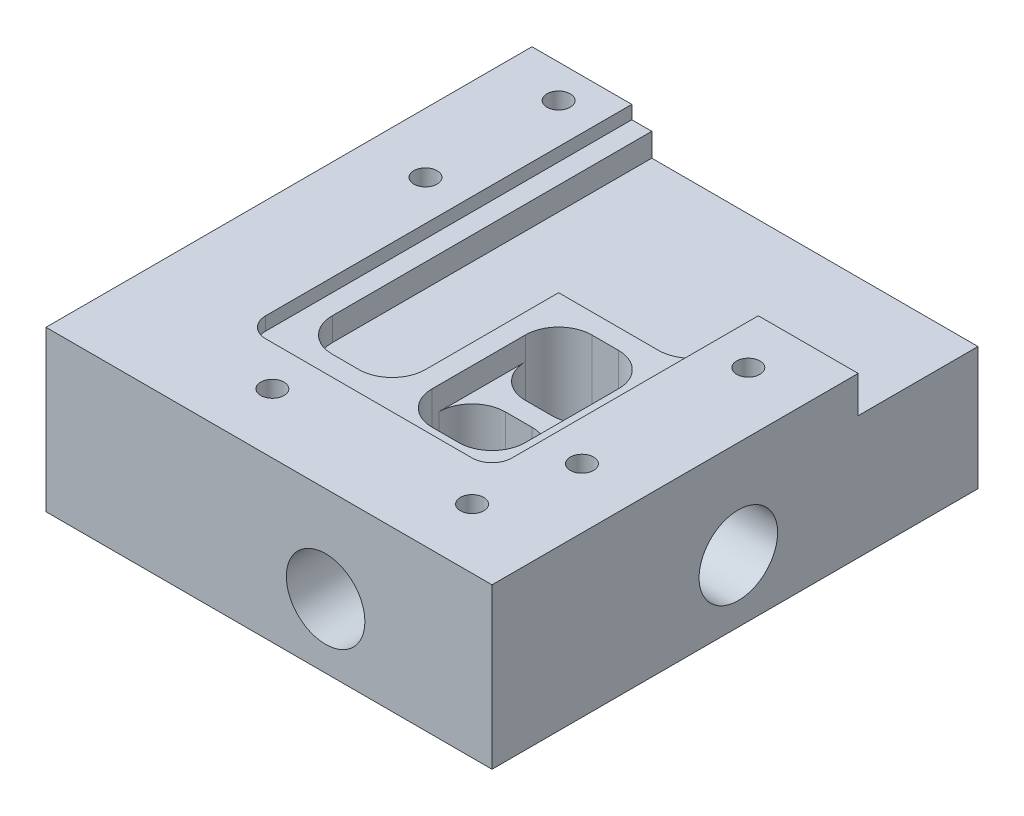
SolidWorks part; units mm, degrees
ref_plane "Front" through (0, 0, 0) normal (0, 0, 1) x (1, 0, 0)
ref_plane "Top" through (0, 0, 0) normal (0, 1, 0) x (1, 0, 0)
ref_plane "Right" through (0, 0, 0) normal (1, 0, 0) x (0, 0, -1)
sketch "Sketch1" plane through (0, 0, 0) normal (0, 1, 0) x (1, 0, 0)
  line L1 (0, 0) -> (67, 0)
  line L2 (0, 0) -> (0, 73)
  line L3 (0, 73) -> (67, 73)
  line L4 (67, 0) -> (67, 73)
  dimension "D1" = 73
  dimension "D2" = 67
extrude "Boss-Extrude1" add sketch "Sketch1" along normal blind 15
sketch "Sketch5" plane through (0, 15, 0) normal (0, 1, 0) x (1, 0, 0)
  line L0 (32, 20) -> (18, 20)
  line L1 (32, 15) -> (52, 15)
  line L2 (32, 20) -> (32, 45)
  line L3 (32, 45) -> (52, 45)
  line L4 (52, 15) -> (52, 45)
  line L5 (18, 20) -> (18, 73)
  line L6 (67, 73) -> (0, 73) construction
  line L7 (0, 0) -> (67, 0) construction
  line L8 (18, 73) -> (15, 73)
  line L9 (67, 0) -> (67, 73) construction
  line L10 (15, 73) -> (15, 15)
  line L11 (15, 15) -> (32, 15)
  dimension "D1" = 20
  dimension "D2" = 30
  dimension "D3" = 15
  dimension "D4" = 15
  dimension "D5" = 5
  dimension "D6" = 3
  dimension "D7" = 37
extrude "Boss-Extrude2" add sketch "Sketch5" along normal blind 3.5
sketch "Sketch6" plane through (0, 18.5, 0) normal (0, 1, 0) x (1, 0, 0)
  line L0 (32, 32.5) -> (21.1856, 32.5) construction
  line L1 (35, 42) -> (49, 42)
  line L2 (35, 42) -> (35, 18)
  line L3 (35, 18) -> (49, 18)
  line L4 (49, 42) -> (49, 18)
  line L5 (32, 45) -> (32, 20) construction
  line L6 (21.1856, 32.5) -> (42, 45) construction
  line L7 (52, 45) -> (32, 45) construction
  line L8 (42, 45) -> (42, -11.0626) construction
  line L9 (15, 15) -> (52, 15) construction
  line L10 (32, 45) -> (32, 20) construction
  line L11 (52, 45) -> (32, 45) construction
  dimension "D1" = 3
  dimension "D2" = 3
  dimension "D3" = 3
extrude "Cut-Extrude2" cut sketch "Sketch6" against normal blind 16
sketch "Sketch8" plane through (0, 0, -18) normal (0, 0, -1) x (-1, 0, 0)
  line L4 (-49, 2.5) -> (-35, 2.5)
  line L5 (-35, 18.5) -> (-49, 18.5)
  line L6 (-49, 18.5) -> (-49, 2.5)
  line L7 (-49, 2.5) -> (-35, 2.5)
  line L8 (-35, 2.5) -> (-35, 18.5)
  line L9 (-35, 18.5) -> (-49, 18.5) construction
  line L10 (-49, 18.5) -> (-49, 2.5) construction
  line L12 (-35, 2.5) -> (-35, 18.5) construction
  circle A0 centre (-42, 6.1554) radius 4
  dimension "D1" = 8
  dimension "D4" = 7
extrude "Cut-Extrude4" cut sketch "Sketch8" against normal through all contours A0
sketch "Sketch9" plane through (49, 0, 0) normal (-1, 0, 0) x (0, 0, 1)
  line L4 (-18, 18.5) -> (-42, 18.5)
  line L5 (-42, 18.5) -> (-42, 2.5)
  line L6 (-42, 2.5) -> (-18, 2.5)
  line L7 (-18, 2.5) -> (-18, 18.5)
  line L8 (-18, 18.5) -> (-42, 18.5) construction
  line L9 (-42, 18.5) -> (-42, 2.5) construction
  line L10 (-42, 2.5) -> (-18, 2.5)
  line L11 (-18, 2.5) -> (-18, 18.5) construction
  circle A0 centre (-37, 5.8531) radius 4
  dimension "D2" = 8
extrude "Cut-Extrude5" cut sketch "Sketch9" against normal through all contours A0 region at (49, 5.9962, -37)
sketch "Sketch10" plane through (35, 37, 0) normal (1, 0, 0) x (0, -1, 0)
  line L1 (22, 32) -> (37, 32)
  line L2 (22, 32) -> (22, 29)
  line L3 (22, 29) -> (37, 29)
  line L4 (37, 32) -> (37, 29)
  line L7 (37, 18) -> (37, 42) construction
  line L8 (34.5, 42) -> (18.5, 42) construction
  dimension "D1" = 3
  dimension "D2" = 15
  dimension "D3" = 10
sketch "Sketch11" plane through (0, 0, 0) normal (0, -1, 0) x (1, 0, 0)
  line L1 (0, 0) -> (67, 0)
  line L2 (0, 0) -> (0, -73)
  line L3 (0, -73) -> (67, -73)
  line L4 (67, 0) -> (67, -73)
extrude "Boss-Extrude4" add sketch "Sketch11" along normal blind 3.5
extrude "Boss-Extrude5" add sketch "Sketch10" along normal up to surface (14 mm away) contours L1 L4 L3 L2 up to face at (49, 9.0589, -32.3333)
sketch "Sketch12" plane through (0, 15, 0) normal (0, 1, 0) x (1, 0, 0)
  line L0 (18.4556, 66) -> (48.6562, 66) construction
  line L1 (18.4556, 66) -> (18.4556, 16.1652) construction
  line L2 (67, 73) -> (18, 73) construction
  line L3 (67, 0) -> (67, 73) construction
  circle A0 centre (18.4556, 66) radius 1.025
  circle A2 centre (48.6562, 66) radius 1.025
  circle A4 centre (36.6635, 53.2215) radius 1.38 construction
  circle A6 centre (18.4556, 16.1652) radius 1.025
  dimension "D4" = 7
  dimension "D1" = 2.05
  dimension "D2" = 30.2006
  dimension "D3" = 49.8348
  dimension "D5" = 18.3438
sketch "Sketch13" plane through (0, 15, 0) normal (0, 1, 0) x (1, 0, 0)
  line L1 (52, 15) -> (67, 15)
  line L2 (52, 15) -> (52, 55)
  line L3 (52, 55) -> (67, 55)
  line L4 (67, 15) -> (67, 55)
  line L5 (15, 15) -> (52, 15) construction
  line L7 (67, 0) -> (67, 73) construction
  dimension "D1" = 15
  dimension "D2" = 40
extrude "Boss-Extrude6" add sketch "Sketch13" along normal blind 5.5
sketch "Sketch16" plane through (0, 0, 0) normal (0, 0, 1) x (1, 0, 0)
  circle A0 centre (42, 6.1554) radius 5.9
  circle A1 centre (42, 6.1554) radius 4 construction
  circle A2 centre (42, 6.1554) radius 4 construction
  dimension "D1" = 11.8
extrude "Cut-Extrude8" cut sketch "Sketch16" against normal blind 10
sketch "Sketch17" plane through (67, 0, 0) normal (1, 0, 0) x (0, 0, -1)
  circle A0 centre (37, 5.8531) radius 4 construction
  circle A1 centre (37, 5.8531) radius 4 construction
  circle A2 centre (37, 5.8531) radius 5.9
  dimension "D1" = 11.8
extrude "Cut-Extrude9" cut sketch "Sketch17" against normal blind 10
fillet "Fillet1" radius 5 8 edges at (49, 10.5, -42) (49, 8.75, -32) (35, 10.5, -18) (35, 10.5, -42) (35, 8.75, -29) (49, 8.75, -29) (49, 10.5, -18) (35, 8.75, -32)
fillet "Fillet2" radius 5 1 edges at (52, 16.75, -45)
sketch "Sketch14" plane through (0, 20.5, 0) normal (0, 1, 0) x (1, 0, 0)
  line L0 (67, 15) -> (67, 55) construction
  line L3 (52, 35) -> (67, 35) construction
  line L4 (52, 55) -> (52, 15) construction
  line L5 (67, 15) -> (67, 55) construction
  circle A0 centre (58, 47.5) radius 1.75
  circle A1 centre (58, 22.5) radius 1.75
  dimension "D1" = 3.5
  dimension "D2" = 25
  dimension "D3" = 9
extrude "Cut-Extrude7" cut sketch "Sketch14" against normal blind 10
sketch "Sketch18" plane through (0, 15, 0) normal (0, 1, 0) x (1, 0, 0)
  line L0 (15, 15) -> (15, 73)
  line L1 (67, 15) -> (15, 15)
  line L2 (67, 15) -> (67, 0)
  line L3 (67, 0) -> (0, 0)
  line L4 (0, 15) -> (0, 0)
  line L5 (67, 73) -> (18, 73) construction
  line L6 (15, 73) -> (0, 73)
  line L7 (0, 73) -> (0, 15)
  line L8 (52, 15) -> (52, 50) construction
  dimension "D1" = 37
extrude "Boss-Extrude7" add sketch "Sketch18" along normal up to surface (5.5 mm away) up to face at (58, 20.5, -20.75)
sketch "Sketch19" plane through (0, 20.5, 0) normal (0, 1, 0) x (1, 0, 0)
  line L0 (9, 68) -> (9, 48) construction
  line L2 (32, 15) -> (15, 15) construction
  line L3 (15, 73) -> (15, 15) construction
  line L5 (25, 9) -> (55, 9) construction
  line L6 (0, 0) -> (0, 73) construction
  circle A0 centre (9, 48) radius 1.75
  circle A1 centre (9, 68) radius 1.75
  circle A2 centre (25, 9) radius 1.75
  circle A3 centre (55, 9) radius 1.75
  dimension "D1" = 3.5
  dimension "D2" = 3.5
  dimension "D6" = 3.5
  dimension "D7" = 3.5
  dimension "D3" = 20
  dimension "D4" = 33
  dimension "D5" = 6
  dimension "D8" = 30
  dimension "D9" = 6
  dimension "D10" = 25
extrude "Cut-Extrude11" cut sketch "Sketch19" against normal blind 10
fillet "Fillet4" radius 3 1 edges at (15, 19.5, -15)
fillet "Fillet5" radius 3 1 edges at (52, 19.5, -15)
fillet "Fillet6" radius 5 2 edges at (18, 16.75, -20) (32, 16.75, -20)
equation "\"d_racor\"= 11.8"
equation "\"h_alphasense\"= 5"
equation "\"h_chamber\"= 13"
equation "\"d_alphasense\" = 32.4mm"
equation "\"d_chamber\"= 19"
equation "\"h_base\"= 25 - \"h_chamber\" - \"h_alphasense\"-1"
equation "\"length_thread\"=10"
equation "\"D2@Sketch9\"=\"d_pipe\""
equation "\"D1@Sketch8\"=\"d_pipe\""
equation "\"length_racor\"= 10"
equation "\"d_pipe\"=8"
equation "\"D1@Sketch12\"= \"d_thread_sck_tap\""
equation "\"D1@Sketch16\"=\"d_racor\""
equation "\"D1@Cut-Extrude8\"=\"length_racor\""
equation "\"D1@Sketch17\"=\"d_racor\""
equation "\"D1@Cut-Extrude9\"=\"length_racor\""
equation "\"clip_thread_hole\" = 4"
equation "\"clip_thread_tap_drill\" = 3.5"
equation "\"D1@Sketch14\"=\"clip_thread_tap_drill\""
equation "\"D1@Cut-Extrude7\"=\"length_thread\""
equation "\"d_thread_sck_hole\"= 2.5"
equation "\"d_thread_sck_tap\" = 2.05"
equation "\"D1@Sketch19\"=\"clip_thread_tap_drill\""
equation "\"D2@Sketch19\"=\"clip_thread_tap_drill\""
equation "\"D1@Cut-Extrude11\"=\"length_thread\""
equation "\"D6@Sketch19\"=\"clip_thread_tap_drill\""
equation "\"D7@Sketch19\"=\"clip_thread_tap_drill\""
